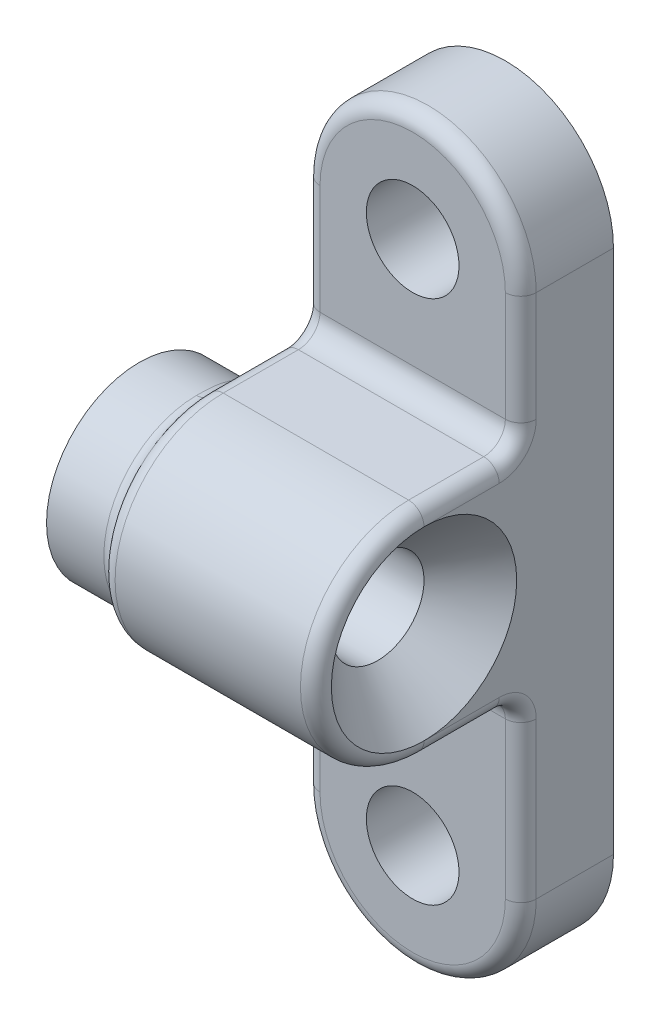
SolidWorks part; units mm, degrees
material "尼龙 101"
ref_plane "前视基准面" through (0, 0, 0) normal (0, 0, 1) x (1, 0, 0)
ref_plane "上视基准面" through (0, 0, 0) normal (0, 1, 0) x (1, 0, 0)
ref_plane "右视基准面" through (0, 0, 0) normal (1, 0, 0) x (0, 0, -1)
sketch "草图1" plane through (0, 0, 0) normal (0, 0, 1) x (1, 0, 0)
  line L0 (-17.9, 4.45) -> (-17.9, -12.55) construction
  line L1 (-14.4, 4.45) -> (-14.4, -12.55)
  line L2 (-21.4, 4.45) -> (-21.4, -12.55)
  arc A0 (-14.4, 4.45) -> (-21.4, 4.45) centre (-17.9, 4.45) ccw
  arc A1 (-21.4, -12.55) -> (-14.4, -12.55) centre (-17.9, -12.55) ccw
  arc A6 (-21.3474, 5.0545) -> (-14.4526, 5.0545) centre (-17.9, 4.45) ccw construction
  arc A7 (-14.4, -12.55) -> (-17.4019, -16.0144) centre (-17.9, -12.55) ccw construction
  circle A8 centre (-17.9, 4.45) radius 1.5
  circle A9 centre (-17.9, -12.55) radius 1.5
  point P2 (-17.9, -4.05)
extrude "凸台-拉伸1" add sketch "草图1" along normal blind 3
sketch "草图2" plane through (-14.4, 0, 0) normal (1, 0, 0) x (0, 0, -1)
  line L0 (-6.1326, 0.1994) -> (-3, 0.1994)
  line L1 (-3, -12.55) -> (-3, 4.45) construction
  line L2 (-6.1326, -6.8006) -> (-3, -6.8006)
  line L3 (-3, -6.8006) -> (-3, 0.1994)
  circle A0 centre (-6.1326, -3.3006) radius 1.5
  circle A1 centre (-6.1326, -3.3006) radius 1.5 construction
  arc A3 (-6.1326, -6.8006) -> (-6.1326, 0.1994) centre (-6.1326, -3.3006) cw
  dimension "D1" = 3.5
extrude "凸台-拉伸2" add sketch "草图2" against normal up to surface (7 mm away) up to face at (-21.4, -4.05, 1.5)
chamfer "倒角1" distance 1.5 angle 45 1 edges at (-14.4, -1.8006, 6.1326)
fillet "圆角1" radius 0.7 2 edges at (-17.9, 0.1994, 3) (-17.9, -6.8006, 3)
fillet "圆角2" radius 0.5 16 edges at (-14.4, 0.4044, 3.205) (-14.4, 0.1994, 4.9163) (-14.4, -3.3006, 9.6326) (-14.4, -6.8006, 4.9163) (-14.4, -7.0056, 3.205) (-14.4, -10.0253, 3) (-17.9, -16.05, 3) (-21.4, -10.0253, 3) (-21.4, -7.0056, 3.205) (-21.4, -6.8006, 4.9163) (-21.4, -3.3006, 9.6326) (-21.4, 0.1994, 4.9163) (-21.4, 0.4044, 3.205) (-17.9, 7.95, 3) (-14.4, 2.6747, 3) (-21.4, 2.6747, 3)
sketch "草图3" plane through (-21.4, 0, 0) normal (-1, 0, 0) x (0, 0, 1)
  circle A0 centre (6.1326, -3.3006) radius 1.5
  circle A1 centre (6.1326, -3.3006) radius 1.5 construction
  circle A2 centre (6.1326, -3.3006) radius 3
  arc A3 (6.1326, -6.3006) -> (6.1326, -0.3006) centre (6.1326, -3.3006) ccw construction
extrude "凸台-拉伸3" add sketch "草图3" along normal blind 2.22
fillet "圆角3" radius 0.5 2 edges at (-21.4, -3.3006, 9.1326) (-21.4, -3.3006, 3.1326)
